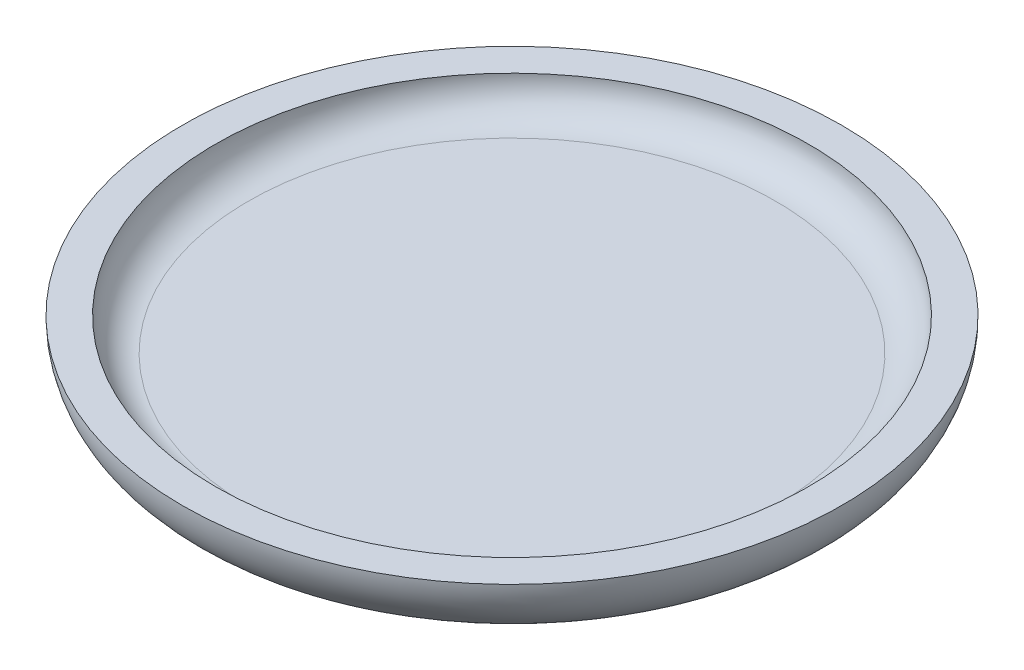
SolidWorks part; units mm, degrees
ref_plane "Front Plane" through (0, 0, 0) normal (0, 0, 1) x (1, 0, 0)
ref_plane "Top Plane" through (0, 0, 0) normal (0, 1, 0) x (1, 0, 0)
ref_plane "Right Plane" through (0, 0, 0) normal (1, 0, 0) x (0, 0, -1)
sketch "Sketch1" plane through (0, 0, 0) normal (0, 1, 0) x (1, 0, 0)
  circle A0 centre (0, 0) radius 63.551
extrude "Boss-Extrude1" add sketch "Sketch1" along normal blind 12.7
fillet "Fillet2" radius 12.7 1 edges at (0, 0, 63.551)
shell "Shell2" thickness 6.35 removed face at (0, 12.7, 63.551)
